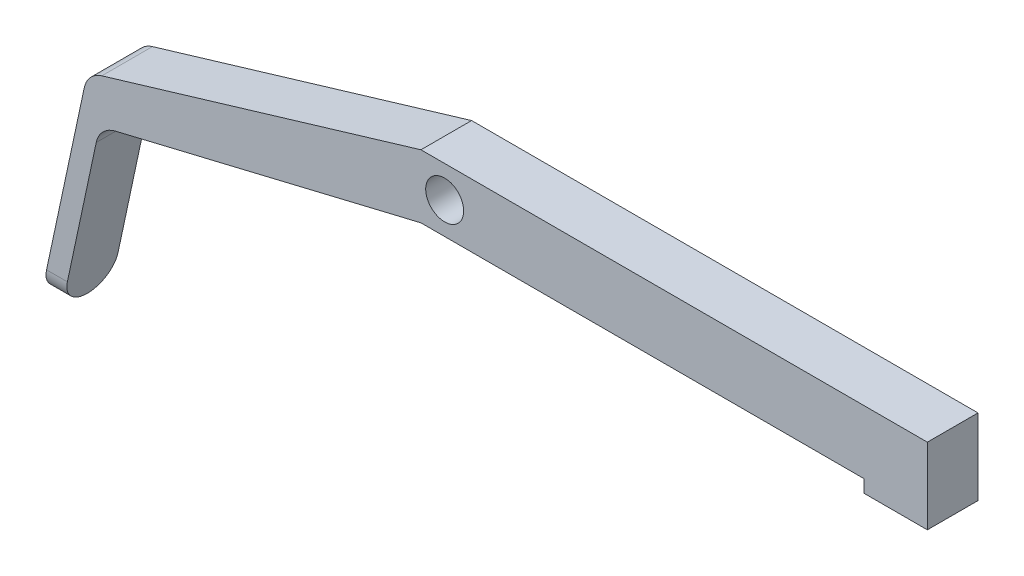
SolidWorks part; units mm, degrees
ref_plane "Front Plane" through (0, 0, 0) normal (0, 0, 1) x (1, 0, 0)
ref_plane "Top Plane" through (0, 0, 0) normal (0, 1, 0) x (1, 0, 0)
ref_plane "Right Plane" through (0, 0, 0) normal (1, 0, 0) x (0, 0, -1)
sketch "Sketch1" plane through (0, 0, 0) normal (0, 0, 1) x (1, 0, 0)
  line L0 (-118.1554, 57.2838) -> (-258.1554, 57.2838) construction
  line L1 (-258.1554, 57.2838) -> (-258.1554, 7.2838) construction
  line L2 (-258.1554, 7.2838) -> (-118.1554, 7.2838) construction
  line L3 (-118.1554, 7.2838) -> (-118.1554, 57.2838) construction
  line L4 (-118.1554, 57.2838) -> (-198.1554, 57.2838)
  line L5 (-198.1554, 57.2838) -> (-250.8455, 41.5119)
  line L6 (-250.8455, 41.5119) -> (-258.1554, 7.2838)
  line L7 (-118.1554, 57.2838) -> (-118.1554, 47.2838)
  line L8 (-118.1554, 47.2838) -> (-198.1554, 47.2838)
  line L9 (-198.1554, 47.2838) -> (-248.9262, 35.1001)
  line L10 (-248.9262, 35.1001) -> (-254.8668, 7.2838)
  line L11 (-254.8668, 7.2838) -> (-258.1554, 7.2838)
  dimension "D1" = 140
  dimension "D2" = 50
  dimension "D3" = 80
  dimension "D4" = 35
  dimension "D5" = 55
  dimension "D6" = 10
  dimension "D7" = 80
  dimension "D8" = 28.4436
  dimension "D9" = 3.2886
extrude "Boss-Extrude1" add sketch "Sketch1" along normal blind 8
sketch "Sketch4" plane through (0, 0, 0) normal (0, 1, 0) x (1, 0, 0)
  line L0 (-118.1554, -8) -> (-128.1554, -8)
  line L1 (-118.1554, -8) -> (-118.1554, -6.5)
  line L2 (-128.1554, -8) -> (-128.1554, -6.5)
  line L3 (-118.1554, -6.5) -> (-128.1554, -6.5)
  line L4 (-198.1554, -8) -> (-118.1554, -8) construction
  line L5 (-118.1554, -4) -> (-264.8028, -4) construction
  line L6 (-118.1554, -8) -> (-118.1554, 0) construction
  line L7 (-118.1554, -6.5) -> (-119.6554, -6.5)
  line L8 (-118.1554, -6.5) -> (-118.1554, -3.9484)
  line L9 (-119.6554, -6.5) -> (-119.6554, -3.9484)
  line L10 (-118.1554, -3.9484) -> (-119.6554, -3.9484)
  line L11 (-119.6554, -1.5) -> (-119.6554, -4.0516)
  line L12 (-118.1554, 0) -> (-118.1554, -1.5)
  line L13 (-118.1554, 0) -> (-128.1554, 0)
  line L14 (-128.1554, 0) -> (-128.1554, -1.5)
  line L15 (-118.1554, -1.5) -> (-128.1554, -1.5)
  dimension "D1" = 10
  dimension "D2" = 1.5
  dimension "D3" = 1.5
sketch "Sketch5" plane through (0, 47.2838, 0) normal (0, -1, 0) x (1, 0, 0)
  line L0 (-119.6554, 1.5) -> (-119.6554, 4.0516) construction
  line L1 (-118.1554, 6.5) -> (-128.1554, 6.5) construction
  line L2 (-128.1554, 8) -> (-128.1554, 6.5) construction
  line L3 (-118.1554, 8) -> (-128.1554, 8) construction
  line L4 (-118.1554, 8) -> (-118.1554, 6.5) construction
  line L5 (-118.1554, 6.5) -> (-119.6554, 6.5) construction
  line L6 (-119.6554, 6.5) -> (-119.6554, 3.9484) construction
  line L7 (-118.1554, 3.9484) -> (-119.6554, 3.9484) construction
  line L8 (-118.1554, 6.5) -> (-118.1554, 3.9484) construction
  line L9 (-118.1554, 0) -> (-118.1554, 1.5) construction
  line L10 (-118.1554, 1.5) -> (-128.1554, 1.5) construction
  line L11 (-128.1554, 0) -> (-128.1554, 1.5) construction
  line L12 (-118.1554, 0) -> (-128.1554, 0) construction
  line L13 (-119.6554, 1.5) -> (-119.6554, 4.0516)
  line L14 (-118.1554, 6.5) -> (-128.1554, 6.5)
  line L15 (-128.1554, 8) -> (-128.1554, 6.5)
  line L16 (-118.1554, 8) -> (-128.1554, 8)
  line L17 (-118.1554, 8) -> (-118.1554, 6.5)
  line L18 (-118.1554, 6.5) -> (-119.6554, 6.5)
  line L19 (-119.6554, 6.5) -> (-119.6554, 3.9484)
  line L20 (-118.1554, 3.9484) -> (-119.6554, 3.9484)
  line L21 (-118.1554, 6.5) -> (-118.1554, 3.9484)
  line L22 (-118.1554, 0) -> (-118.1554, 1.5)
  line L23 (-118.1554, 1.5) -> (-128.1554, 1.5)
  line L24 (-128.1554, 0) -> (-128.1554, 1.5)
  line L25 (-118.1554, 0) -> (-128.1554, 0)
  line L26 (-118.1554, 3.9484) -> (-118.1554, 1.5)
  line M2 (-198.1554, 0) -> (-118.1554, 0)
  line M3 (-118.1554, 0) -> (-118.1554, 8)
  line M4 (-118.1554, 8) -> (-198.1554, 8)
  dimension "D1" = 2.4484
extrude "Boss-Extrude4" add sketch "Sketch5" along normal blind 2 contours L15 L14 M4 M3 | L20 L14 L19 L13 M3 | L23 L20 L13 M3 | L24 L23 M2 M3 region at (-118.9054, 47.2838, 2.7242) region at (-123.1554, 47.2838, 0.75) region at (-118.9054, 47.2838, 5.2242) region at (-123.1554, 47.2838, 7.25)
sketch "Sketch6" plane through (0, 0, 8) normal (0, 0, 1) x (1, 0, 0)
  circle A0 centre (-194.4058, 52.2864) radius 3
  dimension "D1" = 6
extrude "Cut-Extrude1" cut sketch "Sketch6" against normal through all
fillet "Fillet1" radius 4 4 edges at (-248.9262, 35.1001, 4) (-250.8455, 41.5119, 4) (-256.5111, 7.2838, 0) (-256.5111, 7.2838, 8)
